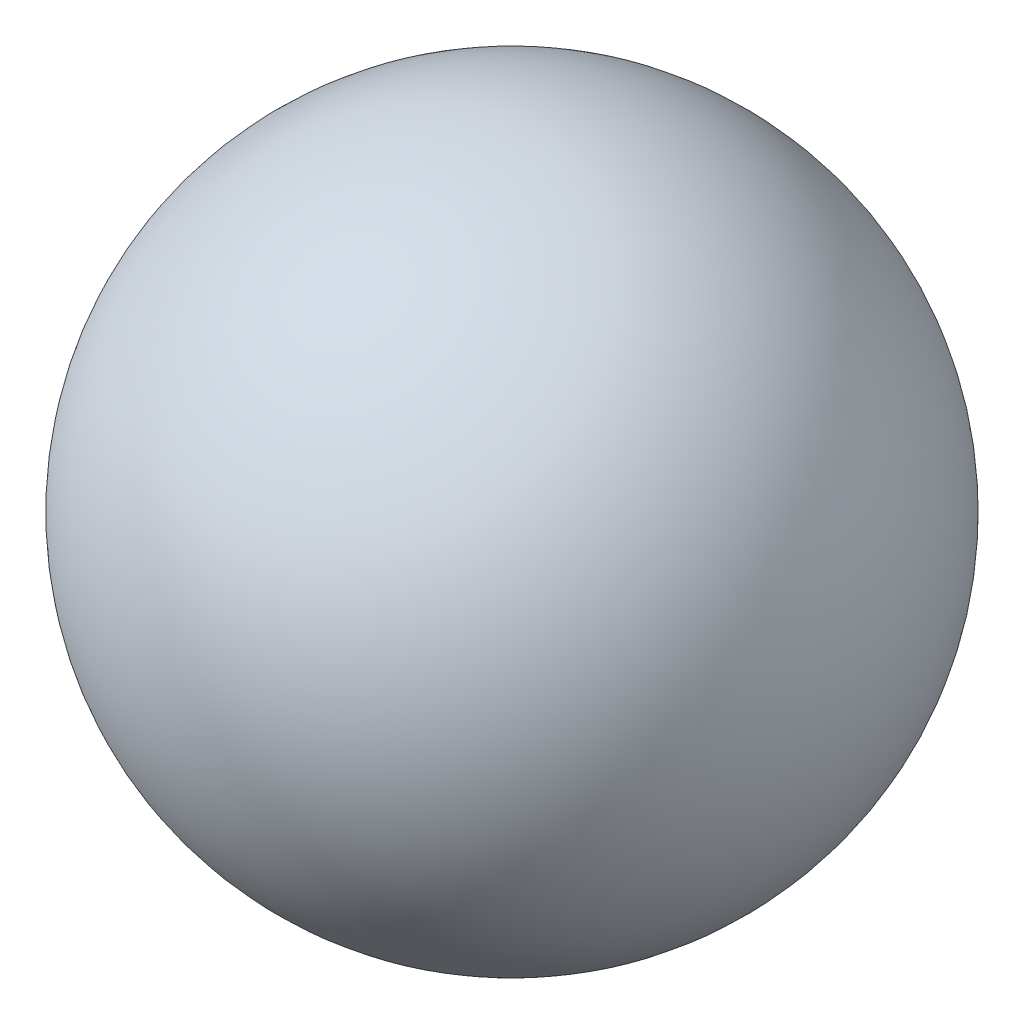
SolidWorks part; units mm, degrees
ref_plane "Front Plane" through (0, 0, 0) normal (0, 0, 1) x (1, 0, 0)
ref_plane "Top Plane" through (0, 0, 0) normal (0, 1, 0) x (1, 0, 0)
ref_plane "Right Plane" through (0, 0, 0) normal (1, 0, 0) x (0, 0, -1)
sketch "Sketch1" plane through (0, 0, 0) normal (0, 0, 1) x (1, 0, 0)
  line L0 (0, -12.5) -> (0, 12.5)
  arc A0 (0, -12.5) -> (0, 12.5) centre (0, 0) ccw
  dimension "D1" = 25
revolve "Revolve1" add sketch "Sketch1" angle 360 about L0 region at (5.3052, 0, 0)
